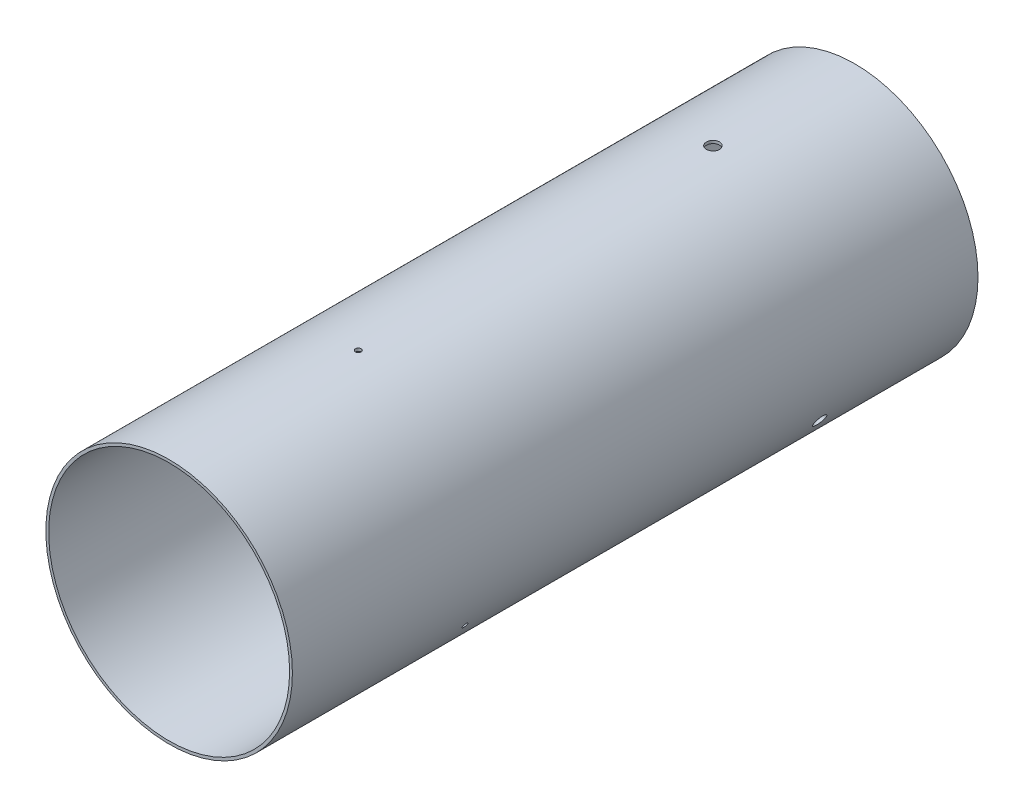
SolidWorks part; units mm, degrees
material "E-Glass Fiber"
ref_plane "Front Plane" through (0, 0, 0) normal (0, 0, 1) x (1, 0, 0)
ref_plane "Top Plane" through (0, 0, 0) normal (0, 1, 0) x (1, 0, 0)
ref_plane "Right Plane" through (0, 0, 0) normal (1, 0, 0) x (0, 0, -1)
sketch "Sketch1" plane through (0, 0, 0) normal (0, 0, 1) x (1, 0, 0)
  circle A0 centre (0, 0) radius 49.6697
  circle A1 centre (0, 0) radius 48.5394
  dimension "D1" = 99.3394
  dimension "D2" = 97.0788
extrude "Boss-Extrude1" add sketch "Sketch1" along normal blind 276.225
ref_plane "Plane1" through (0, 49.6697, 0) normal (0, 1, 0) x (1, 0, 0)
sketch "Sketch2" plane through (0, 49.6697, 0) normal (0, 1, 0) x (1, 0, 0)
  line L0 (0, 0) -> (0, -57.15) construction
  line L1 (0, -57.15) -> (0, 0) construction
  line L2 (-49.6697, -276.225) -> (49.6697, -276.225) construction
  line L3 (0, -57.15) -> (0, -200.025) construction
  line L4 (-48.5394, -276.225) -> (48.5394, -276.225) construction
  circle A0 centre (0, -57.15) radius 2.6289
  circle A2 centre (0, -200.025) radius 1.143
  dimension "D2" = 5.2578
  dimension "D6" = 2.286
  dimension "D1" = 57.15
  dimension "D3" = 276.225
  dimension "D5" = 76.2
extrude "8-32 T-Nut Holes" cut sketch "Sketch2" against normal blind 5.08
sketch "Sketch4" plane through (0, 0, 0) normal (0, 0, -1) x (-1, 0, 0)
  line L0 (0, 49.6697) -> (0, 0) construction
  line L1 (0, 0) -> (43.0152, -24.8348) construction
  circle A0 centre (0, 0) radius 49.6697 construction
  dimension "D1" = 120
ref_plane "Plane2" through (-43.0152, -24.8348, 0) normal (-0.866, -0.5, 0) x (0, 0, 1)
sketch "Sketch3" plane through (-43.0152, -24.8348, 0) normal (-0.866, -0.5, 0) x (0, 0, 1)
  line L0 (0, 0) -> (60.325, 0) construction
  line L1 (60.325, 0) -> (196.85, 0) construction
  line L4 (276.225, -49.6697) -> (276.225, 49.6697) construction
  circle A0 centre (60.325, 0) radius 2.6289
  circle A1 centre (196.85, 0) radius 1.143
  dimension "D3" = 5.2578
  dimension "D4" = 2.286
  dimension "D1" = 60.325
  dimension "D2" = 79.375
extrude "Odd_T-Nut" cut sketch "Sketch3" against normal blind 2.54
pattern_circular "CirPattern1" count 2 every 120 about axis through (0, 0, 276.225) along (0, 0, -1) of "8-32 T-Nut Holes"
